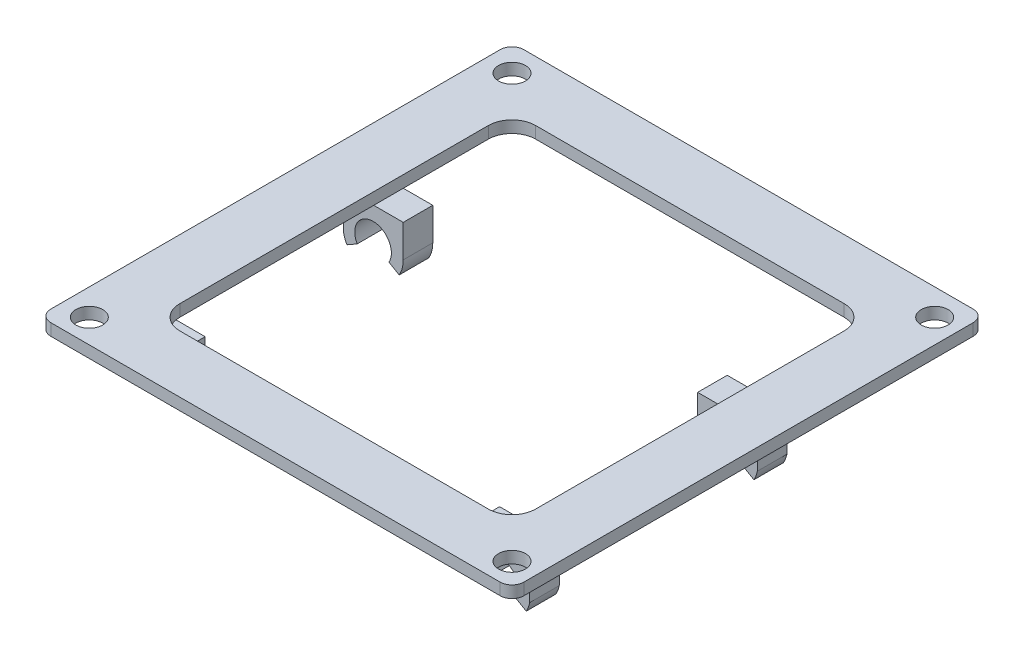
SolidWorks part; units mm, degrees
ref_plane "Front Plane" through (0, 0, 0) normal (0, 0, 1) x (1, 0, 0)
ref_plane "Top Plane" through (0, 0, 0) normal (0, 1, 0) x (1, 0, 0)
ref_plane "Right Plane" through (0, 0, 0) normal (1, 0, 0) x (0, 0, -1)
ref_plane "Plane5" through (0, 1.4, 0) normal (0, 1, 0) x (1, 0, 0)
sketch "Sketch1" plane through (0, 1.4, 0) normal (0, 1, 0) x (1, 0, 0)
  line L0 (-30, 40.97) -> (30, 40.97) construction
  line L1 (35, -16.53) -> (-35, -16.53)
  line L2 (35, -16.53) -> (35, 40.97)
  line L3 (35, 40.97) -> (-35, 40.97)
  line L4 (-35, -16.53) -> (-35, 40.97)
  line L5 (35, -16.53) -> (-35, 40.97) construction
  line L6 (35, 40.97) -> (-35, -16.53) construction
  line L8 (45.85, -16.53) -> (-45.85, -16.53) construction
  line L9 (0, 0) -> (0, 83.8599) construction
  point P0 (-14.8765, 0)
  point P13 (0, 12.22)
  dimension "D1" = 70
extrude "Boss-Extrude1" add sketch "Sketch1" along normal blind 8
sketch "Sketch3" plane through (0, 0, -36.97) normal (0, 0, -1) x (-1, 0, 0)
  line L0 (-35, 1.4) -> (-35, -5.105)
  line L1 (-24.9, -4.1) -> (-24.9, 1.4)
  line L2 (0, 0) -> (0, -23.3047) construction
  line L3 (-35, 1.4) -> (-24.9, 1.4)
  line L4 (-35, 1.4) -> (35, 1.4) construction
  line L5 (35, 1.4) -> (24.9, 1.4)
  line L6 (24.9, -4.1) -> (24.9, 1.4)
  line L7 (35, 1.4) -> (35, -5.105)
  arc A0 (-35, -5.105) -> (-24.9, -4.1) centre (-30, -4.1) ccw
  circle A2 centre (-30, -4.1) radius 3.1
  circle A4 centre (30, -4.1) radius 3.1
  arc A6 (35, -5.105) -> (24.9, -4.1) centre (30, -4.1) cw
  point P2 (-34.2887, -6.8598)
  point P5 (0, 0)
  point P9 (-35, -5.3258)
  dimension "D1" = 2
  dimension "D2" = 6.2
extrude "Boss-Extrude2" add sketch "Sketch3" against normal blind 5 from offset 2 contours A0 L0 L3 L1 A2 | L7 A6 L6 L5 A4 region at (29.95, 1.2536, -36.97) region at (-34.8536, -1.8525, -36.97) offset against normal yes
ref_plane "Plane1" through (0, 0, -13.22) normal (0, 0, 1) x (1, 0, 0)
mirror "Mirror1" about plane through (0, 0, -13.22) normal (0, 0, 1) of "Boss-Extrude2"
sketch "Sketch4" plane through (0, 0, -29.97) normal (0, 0, -1) x (-1, 0, 0)
  line L0 (-30, -4.1) -> (-20, -9.8735)
  line L1 (-20, -9.8735) -> (-40, -9.8735)
  line L2 (-40, -9.8735) -> (-30, -4.1)
  line L3 (0, 0) -> (0, -31.947) construction
  line L4 (20, -9.8735) -> (40, -9.8735)
  line L5 (30, -4.1) -> (20, -9.8735)
  line L6 (40, -9.8735) -> (30, -4.1)
  dimension "D1" = 20
  dimension "D2" = 120
extrude "Cut-Extrude1" cut sketch "Sketch4" against normal blind 63 and the other way blind 10
other "Move Face1" flip direction yes face at (0, 9.4, -12.22) offset 6 parameters "D1"=6
sketch "Sketch5" plane through (0, 3.4, 0) normal (0, 1, 0) x (1, 0, 0)
  line L0 (-40, -16.53) -> (-35, -16.53) construction
  line L1 (40, 63.47) -> (-40, 63.47)
  line L2 (40, 63.47) -> (40, -16.53)
  line L3 (40, -16.53) -> (-40, -16.53)
  line L4 (-40, 63.47) -> (-40, -16.53)
  line L5 (40, 63.47) -> (-40, -16.53) construction
  line L6 (40, -16.53) -> (-40, 63.47) construction
  line L7 (-35, 40.97) -> (-35, -16.53) construction
  line L8 (35, -16.53) -> (40, -16.53) construction
  line L9 (35, -16.53) -> (35, 40.97) construction
  line L10 (-35, -16.53) -> (35, -16.53) construction
  point P0 (0, 23.47)
  point P12 (0, 0)
  dimension "D1" = 80
  dimension "D2" = 80
extrude "Boss-Extrude3" add sketch "Sketch5" against normal blind 2
fillet "Fillet1" radius 2 4 edges at (-40, 2.4, -63.47) (-40, 2.4, 16.53) (40, 2.4, 16.53) (40, 2.4, -63.47)
sketch "Sketch6" plane through (0, 3.4, 0) normal (0, 1, 0) x (1, 0, 0)
  line L0 (35.9551, 59.0149) -> (39.4142, 62.8842) construction
  line L1 (35.9551, 59.0149) -> (-35.5449, 59.0149) construction
  line L2 (35.9551, 59.0149) -> (35.9551, -12.4851) construction
  line L3 (35.9551, -12.4851) -> (-35.5449, -12.4851) construction
  line L4 (-35.5449, 59.0149) -> (-35.5449, -12.4851) construction
  line L5 (-35.5449, -12.4851) -> (-39.4142, -15.9442) construction
  circle A0 centre (35.9551, 59.0149) radius 2.275
  circle A1 centre (35.9551, -12.4851) radius 2.275
  circle A2 centre (-35.5449, 59.0149) radius 2.275
  circle A3 centre (-35.5449, -12.4851) radius 2.275
  arc A4 (40, 61.47) -> (38, 63.47) centre (38, 61.47) ccw construction
  arc A5 (-40, -14.53) -> (-38, -16.53) centre (-38, -14.53) ccw construction
  dimension "D2" = 4.55
  dimension "D1" = 71.5
extrude "Cut-Extrude2" cut sketch "Sketch6" against normal blind 2
sketch "Sketch7" plane through (0, 3.4, 0) normal (0, 1, 0) x (1, 0, 0)
  line L0 (35.9551, 59.0149) -> (-35.5449, -12.4851) construction
  line L2 (-29.8881, -6.8282) -> (30.2982, -6.8282)
  line L3 (-29.8881, -6.8282) -> (-29.8881, 53.3581)
  line L4 (-29.8881, 53.3581) -> (30.2982, 53.3581)
  line L5 (30.2982, -6.8282) -> (30.2982, 53.3581)
  line L6 (-29.8881, -6.8282) -> (30.2982, 53.3581) construction
  line L7 (-29.8881, 53.3581) -> (30.2982, -6.8282) construction
  point P4 (0.2051, 23.2649)
  dimension "D1" = 8
extrude "Cut-Extrude3" cut sketch "Sketch7" against normal blind 2
fillet "Fillet2" radius 4 4 edges at (30.2982, 2.4, -53.3581) (30.2982, 2.4, 6.8282) (-29.8881, 2.4, 6.8282) (-29.8881, 2.4, -53.3581)
